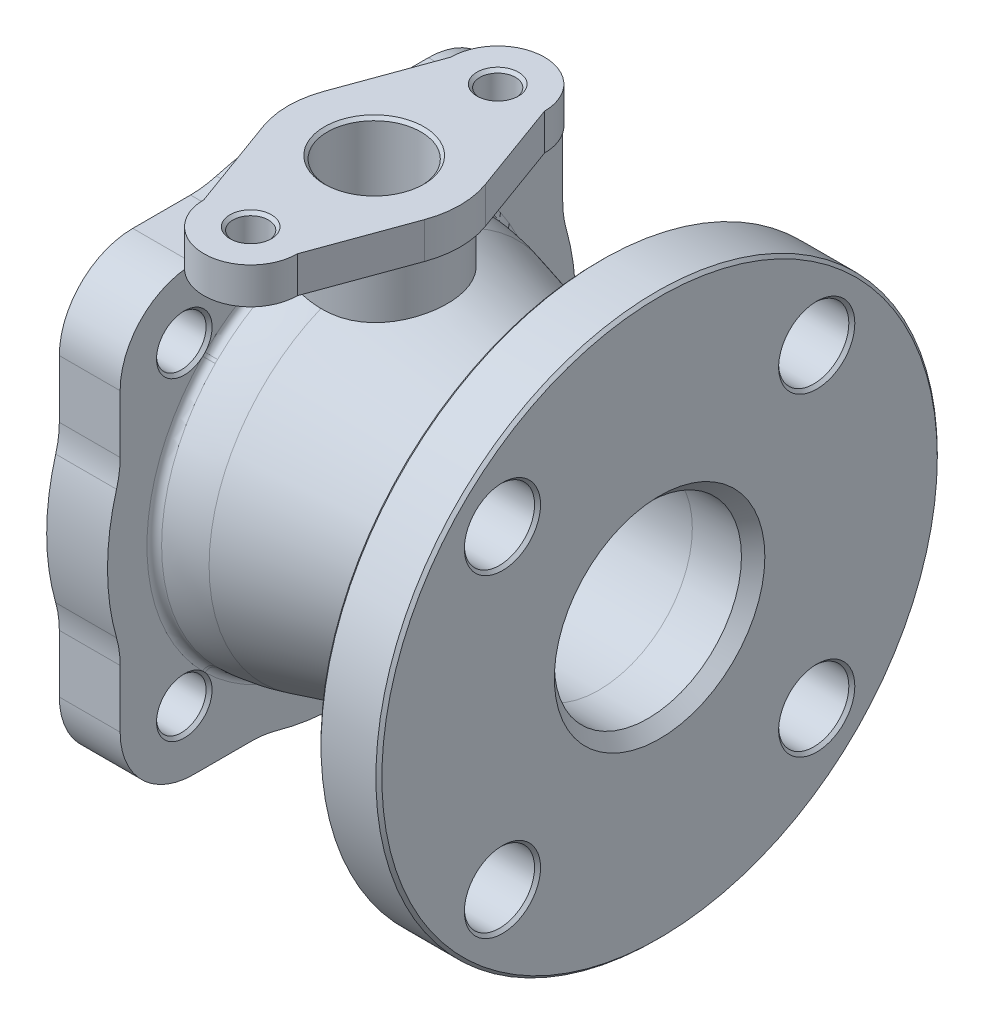
SolidWorks part; units mm, degrees
note: The reader was unsure of these and kept them because the rebuilt part matched: shared geometry of "Croquis7<3>".
ref_plane "Alzado" through (0, 0, 0) normal (0, 0, 1) x (1, 0, 0)
ref_plane "Planta" through (0, 0, 0) normal (0, 1, 0) x (1, 0, 0)
ref_plane "Vista lateral" through (0, 0, 0) normal (1, 0, 0) x (0, 0, -1)
sketch "Croquis1" plane through (0, 0, 0) normal (0, 0, 1) x (1, 0, 0)
  line L0 (0, 25.4) -> (53.975, 25.4)
  line L1 (53.975, 25.4) -> (53.975, 47.625)
  line L2 (53.975, 47.625) -> (52.3748, 46.0248)
  line L3 (52.3748, 46.0248) -> (52.3748, 34.29)
  line L4 (52.3748, 34.29) -> (34.925, 34.29)
  line L5 (34.925, 34.29) -> (16.51, 38.2042)
  line L6 (16.51, 38.2042) -> (16.51, 76.2)
  line L7 (16.51, 76.2) -> (1.6002, 76.2)
  line L8 (1.6002, 76.2) -> (1.6002, 47.6377)
  line L9 (1.6002, 47.6377) -> (0, 46.0375)
  line L10 (0, 46.0375) -> (0, 25.4)
  line L11 (0, 25.4) -> (0, 0) construction
  line L12 (0, 0) -> (54.102, 0) construction
  dimension "D1" = 53.975
  dimension "D2" = 50.8
  dimension "D3" = 95.25
  dimension "D4" = 1.6002
  dimension "D5" = 45
  dimension "D6" = 68.58
  dimension "D7" = 12
  dimension "D8" = 34.925
  dimension "D9" = 16.51
  dimension "D10" = 1.6002
  dimension "D11" = 45
  dimension "D12" = 152.4
  dimension "D13" = 92.075
revolve "Revolución1" add sketch "Croquis1" angle 360 about L12
sketch "Croquis2" plane through (53.975, 0, 0) normal (1, 0, 0) x (0, 0, -1)
  line L0 (0, 25.4) -> (0, 0) construction
  line L1 (0, 0) -> (-42.6562, 42.6562) construction
  line L2 (-42.6562, 42.6562) -> (-53.8815, 53.8815) construction
  line L3 (0, 0) -> (42.6562, 42.6562) construction
  line L4 (0, 0) -> (42.6562, -42.6562) construction
  line L5 (0, 0) -> (-42.6562, -42.6562) construction
  line L6 (-40.132, 60.071) -> (-40.132, 40.132) construction
  line L7 (-40.132, 40.132) -> (-60.071, 40.132) construction
  line L8 (-60.071, 40.132) -> (-60.071, 24.4524)
  line L9 (-40.132, 60.071) -> (-24.4524, 60.071)
  line L10 (40.132, 60.071) -> (24.4524, 60.071)
  line L11 (60.071, 40.132) -> (60.071, 24.4524)
  line L12 (60.071, -40.132) -> (60.071, -24.4524)
  line L13 (40.132, -60.071) -> (24.4524, -60.071)
  line L14 (-40.132, -60.071) -> (-24.4524, -60.071)
  line L15 (-60.071, -40.132) -> (-60.071, -24.4524)
  arc A0 (-61.0507, 17.466) -> (-61.0507, -17.466) centre (0, 0) ccw
  circle A1 centre (0, 0) radius 60.325 construction
  arc A2 (-17.466, -61.0507) -> (17.466, -61.0507) centre (0, 0) ccw
  arc A3 (61.0507, -17.466) -> (61.0507, 17.466) centre (0, 0) ccw
  circle A6 centre (0, 0) radius 25.4 construction
  circle A7 centre (0, 0) radius 76.2 construction
  arc A8 (-40.132, 60.071) -> (-60.071, 40.132) centre (-40.132, 40.132) ccw
  arc A9 (60.071, 40.132) -> (40.132, 60.071) centre (40.132, 40.132) ccw
  arc A10 (40.132, -60.071) -> (60.071, -40.132) centre (40.132, -40.132) ccw
  arc A11 (-60.071, -40.132) -> (-40.132, -60.071) centre (-40.132, -40.132) ccw
  arc A12 (17.466, 61.0507) -> (-17.466, 61.0507) centre (0, 0) ccw
  arc A13 (-24.4524, 60.071) -> (-17.466, 61.0507) centre (-24.4524, 85.471) ccw
  arc A14 (24.4524, 60.071) -> (17.466, 61.0507) centre (24.4524, 85.471) cw
  arc A15 (60.071, 24.4524) -> (61.0507, 17.466) centre (85.471, 24.4524) ccw
  arc A16 (60.071, -24.4524) -> (61.0507, -17.466) centre (85.471, -24.4524) cw
  arc A17 (24.4524, -60.071) -> (17.466, -61.0507) centre (24.4524, -85.471) ccw
  arc A18 (-24.4524, -60.071) -> (-17.466, -61.0507) centre (-24.4524, -85.471) cw
  arc A19 (-60.071, -24.4524) -> (-61.0507, -17.466) centre (-85.471, -24.4524) ccw
  arc A20 (-60.071, 24.4524) -> (-61.0507, 17.466) centre (-85.471, 24.4524) cw
  circle A21 centre (-42.6562, 42.6562) radius 6.731
  circle A22 centre (42.6562, 42.6562) radius 6.731
  circle A23 centre (42.6562, -42.6562) radius 6.731
  circle A24 centre (-42.6562, -42.6562) radius 6.731
  circle A26 centre (0, 0) radius 25.4
  point P25 (0, 0)
  point P43 (0, 0)
  dimension "D1" = 127
  dimension "D2" = 120.65
  dimension "D4" = 39.878
  dimension "D9" = 25.4
  dimension "D10" = 13.462
  dimension "D3" = 45
  dimension "D5" = 40.132
  dimension "D6" = 40.132
  dimension "D7" = 4
  dimension "D8" = 4
extrude "Saliente-Extruir1" add sketch "Croquis2" along normal blind 16.51
sketch "Croquis3" plane through (1.6002, 0, 0) normal (-1, 0, 0) x (0, 0, 1)
  line L0 (0, 25.4) -> (0, 0)
  line L1 (0, 0) -> (-42.6562, 42.6562) construction
  line L2 (0, 0) -> (42.6562, 42.6562) construction
  line L3 (0, 0) -> (42.6562, -42.6562) construction
  line L4 (0, 0) -> (-42.6562, -42.6562) construction
  circle A0 centre (0, 0) radius 60.325 construction
  circle A1 centre (0, 0) radius 25.4
  circle A3 centre (0, 0) radius 25.4
  circle A5 centre (-42.6562, 42.6562) radius 9.525
  circle A9 centre (42.6562, 42.6562) radius 9.525
  circle A12 centre (42.6562, -42.6562) radius 9.525
  circle A14 centre (-42.6562, -42.6562) radius 9.525
  point P14 (0, 0)
  dimension "D2" = 19.05
  dimension "D1" = 0
  dimension "D3" = 4
extrude "Cortar-Extruir1" cut sketch "Croquis3" against normal up to next contours A5 | A9 | A12 | A14
chamfer "Chaflán1" distance 0.8128 angle 45 18 edges at (16.51, -42.6562, -33.1312) (1.6002, -42.6562, -33.1312) (53.975, 42.6562, 35.9252) (70.485, 42.6562, 35.9252) (53.975, 42.6562, -49.3872) (70.485, 42.6562, -49.3872) (53.975, -42.6562, -49.3872) (70.485, -42.6562, -49.3872) (53.975, -42.6562, 35.9252) (70.485, -42.6562, 35.9252) (16.51, -42.6562, 52.1812) (1.6002, -42.6562, 52.1812) (16.51, 42.6562, -33.1312) (1.6002, 42.6562, -33.1312) (16.51, 42.6562, 52.1812) (1.6002, 42.6562, 52.1812) (16.51, 0, 76.2) (1.6002, 0, 76.2)
chamfer "Chaflán2" distance 3.175 angle 45 2 edges at (70.485, 0, -25.4) (0, 0, 25.4)
fillet "Redondeo1" radius 1.524 2 edges at (52.3748, 0, 34.29) (16.51, 0, 38.2042)
sketch "Croquis4" plane through (70.485, 0, 0) normal (1, 0, 0) x (0, 0, -1)
  line L8 (-24.4524, 60.071) -> (-40.132, 60.071)
  line L9 (-60.071, 40.132) -> (-60.071, 24.4524)
  line L10 (-60.071, -24.4524) -> (-60.071, -40.132)
  line L11 (-40.132, -60.071) -> (-24.4524, -60.071)
  line L12 (24.4524, -60.071) -> (40.132, -60.071)
  line L13 (60.071, -40.132) -> (60.071, -24.4524)
  line L14 (60.071, 24.4524) -> (60.071, 40.132)
  line L15 (40.132, 60.071) -> (24.4524, 60.071)
  line L16 (-24.4524, 60.071) -> (-40.132, 60.071)
  line L17 (-60.071, 40.132) -> (-60.071, 24.4524)
  line L18 (-60.071, -24.4524) -> (-60.071, -40.132)
  line L19 (-40.132, -60.071) -> (-24.4524, -60.071)
  line L20 (24.4524, -60.071) -> (40.132, -60.071)
  line L21 (60.071, -40.132) -> (60.071, -24.4524)
  line L22 (60.071, 24.4524) -> (60.071, 40.132)
  line L23 (40.132, 60.071) -> (24.4524, 60.071)
  circle A0 centre (0, 0) radius 25.4 construction
  circle A1 centre (42.6562, -42.6562) radius 6.731 construction
  circle A2 centre (-42.6562, -42.6562) radius 6.731 construction
  circle A3 centre (42.6562, 42.6562) radius 6.731 construction
  circle A4 centre (-42.6562, 42.6562) radius 6.731 construction
  circle A5 centre (0, 0) radius 25.4
  circle A6 centre (42.6562, -42.6562) radius 6.731
  circle A7 centre (-42.6562, -42.6562) radius 6.731
  circle A8 centre (42.6562, 42.6562) radius 6.731
  circle A9 centre (-42.6562, 42.6562) radius 6.731
  arc A16 (-24.4524, 60.071) -> (-17.466, 61.0507) centre (-24.4524, 85.471) ccw
  arc A17 (-40.132, 60.071) -> (-60.071, 40.132) centre (-40.132, 40.132) ccw
  arc A18 (-61.0507, 17.466) -> (-60.071, 24.4524) centre (-85.471, 24.4524) ccw
  arc A19 (-61.0507, 17.466) -> (-61.0507, -17.466) centre (0, 0) ccw
  arc A20 (-60.071, -24.4524) -> (-61.0507, -17.466) centre (-85.471, -24.4524) ccw
  arc A21 (-60.071, -40.132) -> (-40.132, -60.071) centre (-40.132, -40.132) ccw
  arc A22 (-17.466, -61.0507) -> (-24.4524, -60.071) centre (-24.4524, -85.471) ccw
  arc A23 (-17.466, -61.0507) -> (17.466, -61.0507) centre (0, 0) ccw
  arc A24 (24.4524, -60.071) -> (17.466, -61.0507) centre (24.4524, -85.471) ccw
  arc A25 (40.132, -60.071) -> (60.071, -40.132) centre (40.132, -40.132) ccw
  arc A26 (61.0507, -17.466) -> (60.071, -24.4524) centre (85.471, -24.4524) ccw
  arc A27 (61.0507, -17.466) -> (61.0507, 17.466) centre (0, 0) ccw
  arc A28 (60.071, 24.4524) -> (61.0507, 17.466) centre (85.471, 24.4524) ccw
  arc A29 (60.071, 40.132) -> (40.132, 60.071) centre (40.132, 40.132) ccw
  arc A30 (17.466, 61.0507) -> (24.4524, 60.071) centre (24.4524, 85.471) ccw
  arc A31 (17.466, 61.0507) -> (-17.466, 61.0507) centre (0, 0) ccw
  arc A32 (-24.4524, 60.071) -> (-17.466, 61.0507) centre (-24.4524, 85.471) ccw
  arc A33 (-40.132, 60.071) -> (-60.071, 40.132) centre (-40.132, 40.132) ccw
  arc A34 (-61.0507, 17.466) -> (-60.071, 24.4524) centre (-85.471, 24.4524) ccw
  arc A35 (-61.0507, 17.466) -> (-61.0507, -17.466) centre (0, 0) ccw
  arc A36 (-60.071, -24.4524) -> (-61.0507, -17.466) centre (-85.471, -24.4524) ccw
  arc A37 (-60.071, -40.132) -> (-40.132, -60.071) centre (-40.132, -40.132) ccw
  arc A38 (-17.466, -61.0507) -> (-24.4524, -60.071) centre (-24.4524, -85.471) ccw
  arc A39 (-17.466, -61.0507) -> (17.466, -61.0507) centre (0, 0) ccw
  arc A40 (24.4524, -60.071) -> (17.466, -61.0507) centre (24.4524, -85.471) ccw
  arc A41 (40.132, -60.071) -> (60.071, -40.132) centre (40.132, -40.132) ccw
  arc A42 (61.0507, -17.466) -> (60.071, -24.4524) centre (85.471, -24.4524) ccw
  arc A43 (61.0507, -17.466) -> (61.0507, 17.466) centre (0, 0) ccw
  arc A44 (60.071, 24.4524) -> (61.0507, 17.466) centre (85.471, 24.4524) ccw
  arc A45 (60.071, 40.132) -> (40.132, 60.071) centre (40.132, 40.132) ccw
  arc A46 (17.466, 61.0507) -> (24.4524, 60.071) centre (24.4524, 85.471) ccw
  arc A47 (17.466, 61.0507) -> (-17.466, 61.0507) centre (0, 0) ccw
  dimension "D1" = 0
extrude "Saliente-Extruir2" add sketch "Croquis4" along normal blind 16.51 separate body
sketch "Croquis5" plane through (0, 0, 0) normal (0, 0, 1) x (1, 0, 0)
  line L0 (0, 0) -> (187.7004, 0) construction
  line L1 (86.995, -25.4) -> (156.845, -25.4)
  line L2 (86.995, -24.4524) -> (86.995, -40.132) construction
  line L3 (156.845, -25.4) -> (156.845, -38.1)
  line L4 (156.845, -38.1) -> (141.097, -38.1)
  line L5 (141.097, -38.1) -> (100.143, -49.0736)
  line L6 (86.995, -60.071) -> (86.995, -40.132) construction
  line L7 (86.995, -50.8046) -> (107.3647, -50.8046) construction
  line L8 (86.995, -25.4) -> (86.995, -50.8046)
  arc A0 (100.143, -49.0736) -> (86.995, -50.8046) centre (86.995, -0.0046) cw
  dimension "D5" = 50.8
  dimension "D1" = 50.8
  dimension "D2" = 76.2
  dimension "D3" = 15.748
  dimension "D4" = 15
  dimension "D6" = 69.85
revolve "Revolución2" add sketch "Croquis5" angle 360 about L0
sketch "Croquis6" plane through (156.845, 0, 0) normal (1, 0, 0) x (0, 0, -1)
  circle A0 centre (0, 0) radius 76.2 construction
  circle A1 centre (0, 0) radius 76.2
  circle A2 centre (42.6562, -42.6562) radius 9.525 construction
  circle A3 centre (-42.6562, -42.6562) radius 9.525 construction
  circle A4 centre (42.6562, 42.6562) radius 9.525 construction
  circle A5 centre (-42.6562, 42.6562) radius 9.525 construction
  circle A6 centre (42.6562, -42.6562) radius 9.525
  circle A7 centre (-42.6562, -42.6562) radius 9.525
  circle A8 centre (42.6562, 42.6562) radius 9.525
  circle A9 centre (-42.6562, 42.6562) radius 9.525
  circle A10 centre (0, 0) radius 25.4 construction
  circle A11 centre (0, 0) radius 25.4
extrude "Saliente-Extruir3" add sketch "Croquis6" along normal blind 16.51
delete or keep bodies "Sólido-Eliminar/Conservar 3" type delete bodies bodies 103
ref_plane "Plano1" through (0, 69.85, 0) normal (0, 1, 0) x (1, 0, 0)
sketch "Croquis7" plane through (0, 69.85, 0) normal (0, 1, 0) x (1, 0, 0)
  line L0 (70.485, 0) -> (95.885, 0) construction
  line L1 (70.485, 17.466) -> (70.485, -17.466) construction
  line L2 (95.885, -33.528) -> (95.885, 33.528) construction
  line L3 (83.185, 33.528) -> (73.9856, 8.2529)
  line L4 (108.585, 33.528) -> (117.7844, 8.2529)
  line L5 (108.585, -33.528) -> (117.7844, -8.2529)
  line L6 (83.185, -33.528) -> (73.9856, -8.2529)
  circle A0 centre (95.885, 0) radius 12.7
  circle A1 centre (95.885, 33.528) radius 12.7
  circle A2 centre (95.885, 33.528) radius 4.826
  circle A3 centre (95.885, -33.528) radius 4.826
  circle A4 centre (95.885, -33.528) radius 12.7
  arc A5 (117.7844, 8.2529) -> (117.7844, -8.2529) centre (95.1096, 0) cw
  arc A6 (73.9856, 8.2529) -> (73.9856, -8.2529) centre (96.6604, 0) ccw
  point P19 (120.7882, 0)
  point P22 (70.9818, 0)
  dimension "D1" = 25.4
  dimension "D4" = 25.4
  dimension "D5" = 9.652
  dimension "D7" = 24.13
  dimension "D2" = 25.4
  dimension "D3" = 33.528
  dimension "D6" = 20
extrude "Saliente-Extruir4" add sketch "Croquis7" against normal blind 9.8552 contours L3 A6 L6 A4 L5 A5 L4 A1 A0 | A1 A2 | A4 A3 | A0
sketch "Croquis8" plane through (0, 69.85, 0) normal (0, 1, 0) x (1, 0, 0)
  circle A0 centre (96.6604, 0) radius 19.05
  dimension "D1" = 38.1
extrude "Saliente-Extruir5" add sketch "Croquis8" against normal up to surface (23.7548 mm away)
extrude "Cortar-Extruir2" cut sketch "Croquis7<3>" against normal up to next contours A0
sketch "Croquis7<3>" plane through (0, 69.85, 0) normal (0, 1, 0) x (1, 0, 0) same geometry as "Croquis7"
chamfer "Chaflán3" distance 0.8128 angle 45 13 edges at (70.485, -42.6562, 35.9252) (86.995, -42.6562, 35.9252) (70.485, -42.6562, -49.3872) (86.995, -42.6562, -49.3872) (70.485, 42.6562, 35.9252) (86.995, 42.6562, 35.9252) (70.485, 42.6562, -49.3872) (86.995, 42.6562, -49.3872) (95.885, 69.85, 12.7) (95.885, 69.85, 38.354) (95.885, 59.9948, 38.354) (95.885, 69.85, -28.702) (95.885, 59.9948, -28.702)
chamfer "Chaflán4" distance 0.8128 angle 45 10 edges at (156.845, -42.6562, 33.1312) (173.355, -42.6562, 33.1312) (156.845, -42.6562, -52.1812) (173.355, -42.6562, -52.1812) (156.845, 42.6562, 33.1312) (173.355, 42.6562, 33.1312) (156.845, 42.6562, -52.1812) (173.355, 42.6562, -52.1812) (173.355, 0, -76.2) (156.845, 0, -76.2)
chamfer "Chaflán5" distance 3.175 angle 45 1 edges at (173.355, 0, -25.4)
chamfer "Chaflán6" distance 3.175 angle 45 1 edges at (70.485, 0, -25.4)
fillet "Redondeo2" radius 2.032 3 edges at (141.097, 0, 38.1) (156.845, 0, 38.1) (86.995, -50.8046, 0)
